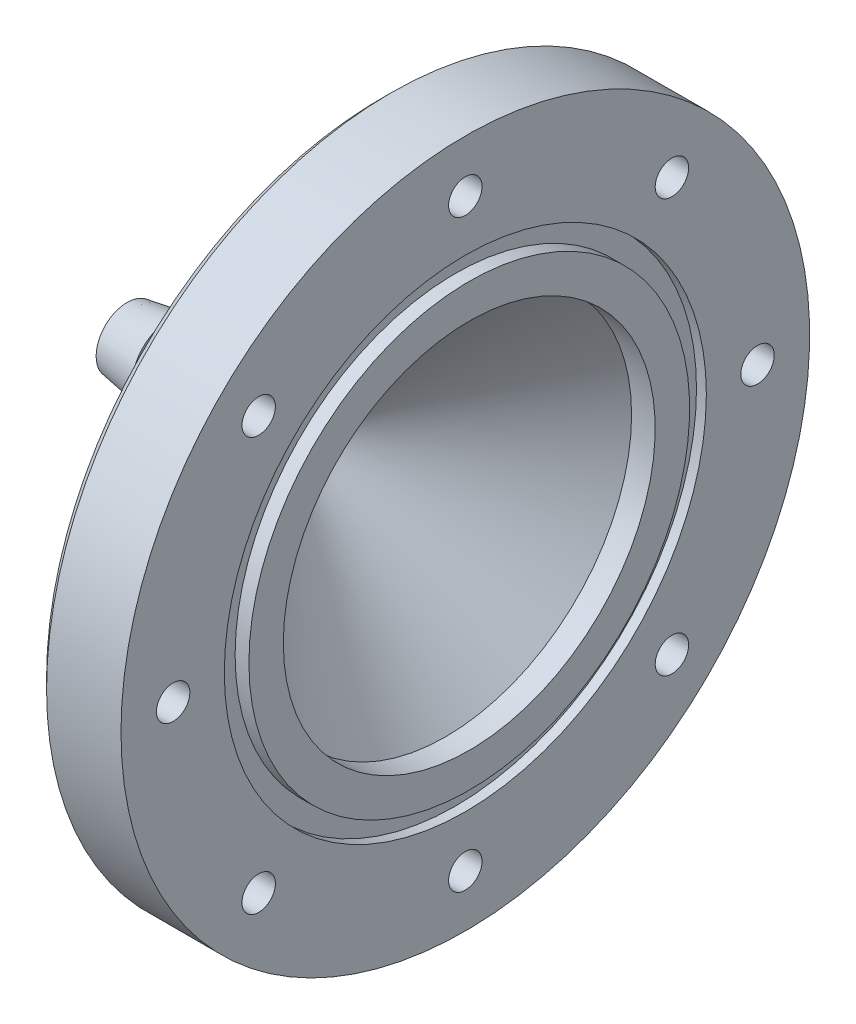
SolidWorks part; units mm, degrees
ref_plane "Front Plane" through (0, 0, 0) normal (0, 0, 1) x (1, 0, 0)
ref_plane "Top Plane" through (0, 0, 0) normal (0, 1, 0) x (1, 0, 0)
ref_plane "Right Plane" through (0, 0, 0) normal (1, 0, 0) x (0, 0, -1)
sketch "Sketch1" plane through (0, 0, 0) normal (0, 0, 1) x (1, 0, 0)
  line L0 (-801.9206, 0) -> (36107.5283, 0) construction
  line L3 (-13.5729, 3.85) -> (-13.5729, 3.15)
  line L8 (-17.9062, 1.9) -> (0, 1.9)
  line L9 (-17.9062, 1.9) -> (-17.9062, 3.15)
  line L10 (16.4699, 24.5) -> (16.4699, 35)
  line L12 (16.4699, 35) -> (7.9039, 35)
  line L16 (16.4699, 24.5) -> (15.4699, 24.5)
  line L17 (15.4699, 24.5) -> (15.4699, 18.9)
  line L18 (7.9039, 35) -> (7.9039, 18.9)
  line L20 (0, 1.9) -> (14.4699, 18.9)
  line L21 (-17.9062, 3.15) -> (-13.5729, 3.85)
  line L22 (14.4699, 18.9) -> (15.4699, 18.9)
  line L23 (-13.5729, 3.15) -> (-9.2395, 3.85)
  line L25 (-9.2395, 3.15) -> (-4.9062, 3.85)
  line L26 (-9.2395, 3.85) -> (-9.2395, 3.15)
  line L27 (-4.9062, 3.85) -> (7.9039, 18.9)
  line L33 (15.4699, 22.4) -> (16.8699, 22.4)
  line L34 (16.8699, 22.4) -> (16.8699, 18.9)
  line L35 (16.8699, 18.9) -> (15.4699, 18.9)
  dimension "D3" = 1
  dimension "D2" = 7.7
  dimension "D6" = 3.8
  dimension "D7" = 6.3
  dimension "D5" = 35
  dimension "D8" = 24.5
  dimension "D4" = 5
  dimension "D9" = 1
  dimension "D11" = 13
  dimension "D12" = 8.566
  dimension "D16" = 3.5
  dimension "D10" = 2.1
  dimension "D13" = 0.4
revolve "Revolve17" add sketch "Sketch1" angle 360 about L0 region at (-14.0501, 3.5, 0) region at (16.1699, 20.65, 0)
sketch "Sketch4" plane through (7.9039, 0, 0) normal (-1, 0, 0) x (0, 0, 1)
  line L0 (0, 18.9) -> (0, 35) construction
  circle A0 centre (0, 0) radius 29.7 construction
  circle A1 centre (0, 0) radius 18.9 construction
  circle A2 centre (0, 0) radius 35 construction
  point P3 (0, 29.7)
  point P7 (29.7, 0)
  point P12 (-29.7, 0)
  point P13 (0, -29.7)
  point P22 (-21.0011, 20.8472)
  point P25 (21.0011, 20.8472)
  point P28 (21.0011, -21.1549)
  point P31 (-21.0011, -21.1549)
  dimension "D1" = 5.3
  dimension "D2" = 5.3
hole_wizard "CBORE for M3 Hex Socket Head Cap Screw2" positions "Sketch4" profile "Sketch5" counterbore size "M3" standard "ISO"
sketch "Sketch5" plane through (7.9039, -21.1549, -21.0011) normal (0, 1, 0) x (0, 0, 1)
  line L0 (0, 0) -> (0, 9.5875)
  line L1 (0, 9.5875) -> (1.7, 8.566)
  line L2 (1.7, 8.566) -> (1.7, 3.4)
  line L3 (1.7, 3.4) -> (3.25, 3.4)
  line L4 (3.25, 3.4) -> (3.25, 0)
  line L5 (3.25, 0) -> (0, 0)
  line L10 (0, 9.5875) -> (-1.7, 8.566) construction
  line L11 (0, -6.35) -> (0, 107.95) construction
  dimension "Hole Dia." = 3.4
  dimension "Hole Depth" = 8.566
  dimension "C'Bore Dia." = 6.5
  dimension "C'Bore Depth" = 3.4
  dimension "Drill Angle" = 118
chamfer "Chamfer1" distance 1 angle 45 1 edges at (7.9039, 0, 35)
sketch "Sketch6" plane through (16.4699, 0, 0) normal (1, 0, 0) x (0, 0, -1)
  line L0 (0, 35) -> (0, 24.5)
  circle A0 centre (0, 0) radius 35
  circle A1 centre (0, 0) radius 35 construction
  circle A2 centre (0, 0) radius 24.5 construction
equation "\"D9@Sketch1\"=\"D3@Sketch1\""
